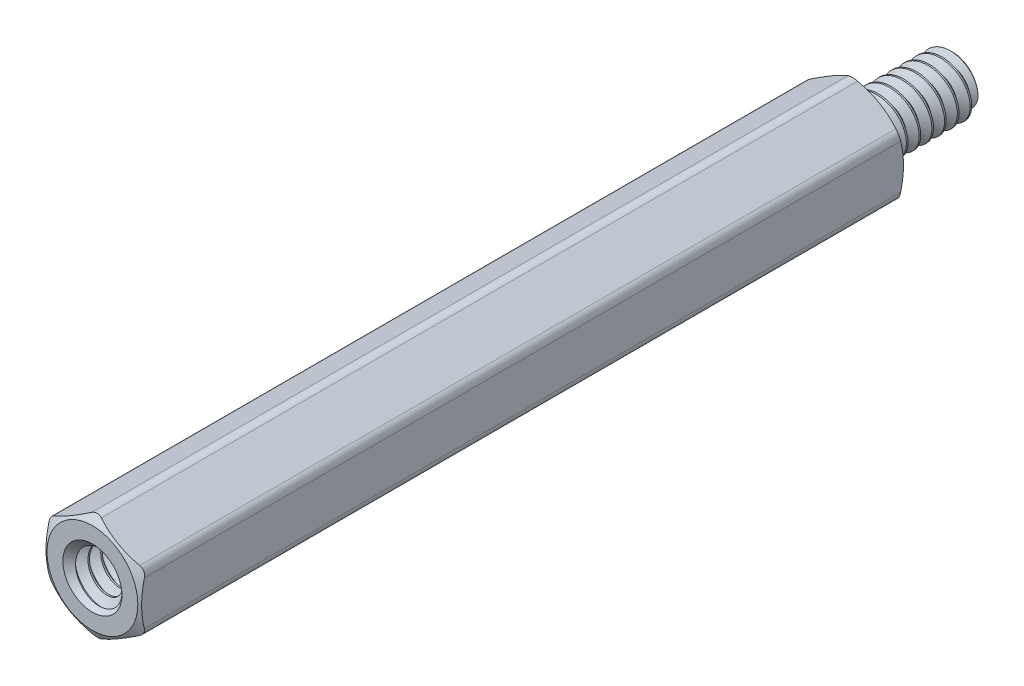
SolidWorks part; units mm, degrees
ref_plane "Front Plane" through (0, 0, 0) normal (0, 0, 1) x (1, 0, 0)
ref_plane "Top Plane" through (0, 0, 0) normal (0, 1, 0) x (1, 0, 0)
ref_plane "Right Plane" through (0, 0, 0) normal (1, 0, 0) x (0, 0, -1)
sketch "Sketch1" plane through (0, 0, 0) normal (0, 0, 1) x (1, 0, 0)
  line L1 (2.3813, 1.3748) -> (0, 2.7496)
  line L2 (0, 2.7496) -> (-2.3812, 1.3748)
  line L3 (-2.3812, 1.3748) -> (-2.3812, -1.3748)
  line L4 (-2.3812, -1.3748) -> (0, -2.7496)
  line L5 (0, -2.7496) -> (2.3813, -1.3748)
  line L6 (2.3813, -1.3748) -> (2.3813, 1.3748)
  circle A0 centre (0, 0) radius 2.3812 construction
  point P10 (0, -2.3812)
  dimension "Hex Size" = 4.7625
sketch "Sketch2" plane through (0, 0, 0) normal (1, 0, 0) x (0, 0, -1)
  line L0 (4.7625, 0) -> (-38.1, 0) construction
  line L2 (0, 1.4224) -> (0, -1.4224) construction
  line L3 (-31.75, 1.4224) -> (-31.75, -1.4224) construction
  line L4 (-38.6953, 1.4911) -> (-38.3778, 0.9412) construction
  line L5 (-38.3778, 0.9412) -> (-38.0603, 1.4911) construction
  line L6 (-38.0603, 1.4911) -> (-38.6953, 1.4911) construction
  line L7 (-38.6556, 1.4224) -> (-38.1, 1.4224) construction
  line L8 (-38.4175, 1.01) -> (-38.3381, 1.01) construction
  line L9 (-38.3778, 1.01) -> (-38.3778, 0.9412) construction
  line L10 (-38.3778, 1.4224) -> (-38.3778, 1.4911) construction
  line L11 (4.7228, 1.4911) -> (5.3578, 1.4911) construction
  line L12 (5.3578, 1.4911) -> (5.0403, 0.9412) construction
  line L13 (5.0403, 0.9412) -> (4.7228, 1.4911) construction
  line L14 (4.7625, 1.4224) -> (5.3181, 1.4224) construction
  line L15 (5.0006, 1.01) -> (5.08, 1.01) construction
  line L16 (5.0403, 1.01) -> (5.0403, 0.9412) construction
  line L17 (5.0403, 1.4224) -> (5.0403, 1.4911) construction
  line L18 (0, 2.7496) -> (-38.1, 2.7496) construction
  point P6 (0, 0)
  point P9 (-31.75, 0)
  dimension "Length" = 38.1
sketch "Sketch3" plane through (0, 0, 0) normal (1, 0, 0) x (0, 0, -1)
  line L0 (-31.75, 0) -> (4.7625, 0)
  line L1 (-31.75, 1.4224) -> (-31.75, -1.4224) construction
  line L2 (4.7625, 0) -> (4.7625, 1.2637)
  line L3 (4.7625, 1.2637) -> (4.6038, 1.4224)
  line L4 (4.6038, 1.4224) -> (0.8096, 1.4224)
  line L5 (0.8096, 1.4224) -> (0.5715, 1.01)
  line L6 (-31.75, 0) -> (-31.75, 1.2636)
  line L7 (-31.75, 1.2636) -> (-31.9088, 1.4224)
  line L8 (-31.9088, 1.4224) -> (-37.9413, 1.4224)
  line L9 (-37.9413, 1.4224) -> (-38.1, 1.5811)
  line L10 (4.6038, 0) -> (4.6038, -1.4224) construction
  line L11 (-38.1, 1.5811) -> (-38.1, 2.3812)
  line L12 (-38.1, 2.3812) -> (0, 2.3812)
  line L14 (0.5715, 1.01) -> (0.1587, 1.01)
  line L15 (0, 1.1687) -> (0, 2.3812)
  arc A0 (0, 1.1687) -> (0.1587, 1.01) centre (0.1587, 1.1687) ccw
  point P5 (-38.1, -2.3812)
  point P8 (-36.5125, -1.4224)
  point P9 (3.175, -1.4224)
  point P27 (0, 1.01)
  dimension "D4" = 0.1588
  dimension "D2" = 0.1588
  dimension "D1" = 45
  dimension "D6" = 1.5875
  dimension "D7" = 60
  dimension "D3" = 1.5875
  dimension "D5" = 0.5715
revolve "Revolve1" add sketch "Sketch3" angle 360 about L0 region at (0, 1.2027, 15.8414)
sketch "Sketch4" plane through (0, 0, 38.1) normal (0, 0, 1) x (1, 0, 0)
  line L0 (0, 2.3812) -> (0, 1.4224) construction
  line L1 (-2.3812, 1.3748) -> (-2.3812, -1.3748)
  line L2 (-2.3812, -1.3748) -> (0, -2.7496)
  line L3 (0, -2.7496) -> (2.3812, -1.3748)
  line L4 (2.3812, -1.3748) -> (2.3812, 1.3748)
  line L5 (2.3812, 1.3748) -> (0, 2.7496)
  line L6 (0, 2.7496) -> (-2.3812, 1.3748)
  circle A0 centre (0, 0) radius 2.3812 construction
  circle A1 centre (0, 0) radius 1.9018
  circle A2 centre (0, 0) radius 2.3812 construction
  point P16 (0, 1.9018)
extrude "Boss-Extrude1" add sketch "Sketch4" against normal up to surface (38.1 mm away) up to face at (0, 2.3812, 0)
sketch "Sketch5" plane through (0, 0, 38.1) normal (0, 0, 1) x (1, 0, 0)
  line L0 (-0.8159, 1.1652) -> (0.8159, -1.1652) construction
  line L1 (0, 1.4224) -> (0, -1.4224) construction
  line L3 (0, -2.9435) -> (0, 2.9435) construction
  circle A0 centre (0, 0) radius 2.2622
  point P11 (0.8159, -1.1652)
  dimension "D1" = 4.5244
  dimension "D2" = 35
extrude "Cut-Extrude1" cut sketch "Sketch5" against normal through all draft 60 flip side to cut
sketch "Sketch6" plane through (0, 0, 0) normal (0, 0, -1) x (-1, 0, 0)
  circle A0 centre (0, 0) radius 2.2622
  circle A1 centre (0, 0) radius 2.2622 construction
extrude "Cut-Extrude2" cut sketch "Sketch6" against normal through all draft 60 flip side to cut
fillet "Fillet1" radius 0.4763 6 edges at (0, 2.7496, 19.05) (-2.3812, -1.3748, 19.05) (0, -2.7496, 19.05) (2.3812, -1.3748, 19.05) (2.3812, 1.3748, 19.05) (-2.3812, 1.3748, 19.05)
sketch "Drawing1" plane through (0, 0, 0) normal (1, 0, 0) x (0, 0, -1)
  line L0 (-38.1, 1.4224) -> (-31.75, 1.4224) construction
  line L1 (-31.75, 1.4224) -> (-31.75, -1.4224) construction
  line L2 (-31.75, -1.4224) -> (-38.1, -1.4224) construction
sketch "Sketch7" plane through (0, 0, 0) normal (-1, 0, 0) x (0, 0, 1)
  line L0 (-5.0006, 1.01) -> (-5.08, 1.01)
  line L1 (-5.08, 1.01) -> (-5.338, 1.4568)
  line L2 (-5.3578, 1.4911) -> (-5.0403, 0.9412) construction
  line L3 (-5.338, 1.4568) -> (-4.7427, 1.4568)
  line L4 (-5.0403, 0.9412) -> (-4.7228, 1.4911) construction
  line L5 (-4.7427, 1.4568) -> (-5.0006, 1.01)
  line L6 (-5.0403, 1.4224) -> (-5.0403, 1.4911) construction
  point P12 (-5.0403, 1.4568)
sketch "Sketch8" plane through (0, 0, -4.7625) normal (0, 0, -1) x (-1, 0, 0)
  circle A0 centre (0, 0) radius 1.4224
curve "Helix/Spiral1" pitch 0.635 height 4.6196 radius 1.4224 centre (0, 0, -4.7625) axis (0, 0, 1) start towards (0, 1, 0)
sweep "Cut-Sweep1" cut profiles "Sketch7" path "Helix/Spiral1" align with end faces yes
sketch "Sketch9" plane through (0, 0, 31.75) normal (0, 0, 1) x (1, 0, 0)
  circle A0 centre (0, 0) radius 1.5811
extrude "Boss-Extrude2" add sketch "Sketch9" along normal up to surface (6.35 mm away) up to face at (0, 1.5811, 38.1)
sketch "Sketch10" plane through (0, 0, 0) normal (1, 0, 0) x (0, 0, -1)
  line L0 (4.7625, 0) -> (-38.1, 0) construction
  line L1 (-31.75, 1.4224) -> (-38.1, 1.4224)
  line L2 (-31.75, 1.4224) -> (-31.75, 0)
  line L3 (-31.75, 0) -> (-38.1, 0)
  line L4 (-38.1, 1.4224) -> (-38.1, 0)
revolve "Revolve2" add sketch "Sketch10" angle 360 about L0
sketch "Sketch11" plane through (0, 0, 38.1) normal (0, 0, 1) x (1, 0, 0)
  circle A0 centre (0, 0) radius 1.4224
  circle A1 centre (0, 0) radius 1.4224 construction
sketch "Sketch12" plane through (0, 0, 0) normal (1, 0, 0) x (0, 0, -1)
  line L0 (-38.4175, 1.01) -> (-38.3381, 1.01)
  line L1 (-38.3381, 1.01) -> (-38.0802, 1.4568)
  line L2 (-38.3778, 0.9412) -> (-38.0603, 1.4911) construction
  line L3 (-38.0802, 1.4568) -> (-38.6755, 1.4568)
  line L4 (-38.6953, 1.4911) -> (-38.3778, 0.9412) construction
  line L5 (-38.6755, 1.4568) -> (-38.4175, 1.01)
  line L6 (-38.3778, 1.4224) -> (-38.3778, 1.4911) construction
  point P12 (-38.3778, 1.4568)
curve "Helix/Spiral2" pitch 0.635 height 6.985 radius 1.4224 centre (0, 0, 38.1) axis (0, 0, -1) start towards (0, 1, 0)
sweep "Cut-Sweep2" cut profiles "Sketch12" path "Helix/Spiral2" align with end faces yes
combine bodies "Combine1" operation type subtract main body 113 bodies to subtract 114
sketch "Sketch13" plane through (0, 0, 38.1) normal (0, 0, 1) x (1, 0, 0)
  circle A0 centre (0, 0) radius 1.4732
  dimension "D1" = 0.0508
extrude "Cut-Extrude3" cut sketch "Sketch13" against normal through all draft 45
equation "\"Thread Pitch (B)/8@Sketch2\"=\"Thread Pitch (B)@Sketch2\"/8"
equation "\"Thread Pitch (A)/8@Sketch2\"=\"Thread Pitch (A)@Sketch2\"/8"
equation "\"D1@Sketch5\" = \"Hex Size@Sketch1\" * .95"
equation "\"D1@Fillet1\" = \"Hex Size@Sketch1\" * .1"
equation "\"D2@Sketch3\" = \"Thread Pitch (A)@Sketch2\" * .25"
equation "\"D4@Sketch3\" = \"D2@Sketch3\""
equation "\"D6@Sketch3\" = \"Thread Pitch (A)@Sketch2\" * 2.5"
equation "\"D3@Helix/Spiral1\" = \"Thread Length (A)@Sketch2\" - \"D5@Sketch3\" * .25"
equation "\"D4@Helix/Spiral1\" = \"Thread Pitch (A)@Sketch2\""
equation "\"D3@Sketch3\" = \"Thread Pitch (B)@Sketch2\" * 2.5"
equation "\"D5@Sketch3\" = \"Thread Length (A)@Sketch2\" * .12"
equation "\"D3@Helix/Spiral2\" = \"Minimum Thread Length (B)@Sketch2\" + \"Thread Pitch (B)@Sketch2\""
equation "\"D4@Helix/Spiral2\" = \"Thread Pitch (B)@Sketch2\""
